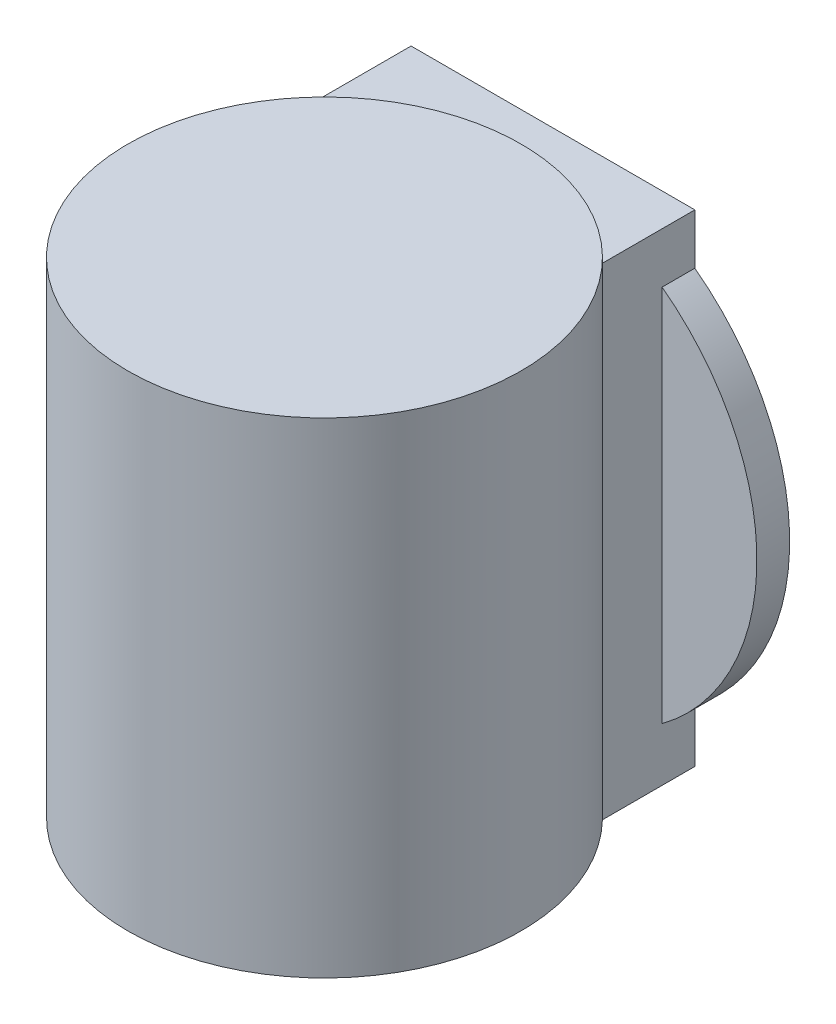
SolidWorks part; units mm, degrees
ref_plane "Front Plane" through (0, 0, 0) normal (0, 0, 1) x (1, 0, 0)
ref_plane "Top Plane" through (0, 0, 0) normal (0, 1, 0) x (1, 0, 0)
ref_plane "Right Plane" through (0, 0, 0) normal (1, 0, 0) x (0, 0, -1)
sketch "Sketch1" plane through (0, 0, 0) normal (0, 1, 0) x (1, 0, 0)
  circle A0 centre (0, 0) radius 0.03
extrude "Boss-Extrude1" add sketch "Sketch1" along normal blind 0.037 and the other way blind 0.037
sketch "Sketch2" plane through (0, 0, 0) normal (0, 0, 1) x (1, 0, 0)
  line L0 (-0.03, -0.037) -> (0.03, -0.037) construction
  line L1 (0.0215, 0.0365) -> (-0.0218, 0.0365)
  line L2 (0.0215, 0.0365) -> (0.0215, -0.037)
  line L3 (0.0215, -0.037) -> (-0.0218, -0.037)
  line L4 (-0.0218, 0.0365) -> (-0.0218, -0.037)
  circle A0 centre (0, 0) radius 0.036
extrude "Boss-Extrude2" add sketch "Sketch2" against normal blind 0.035 contours L2 L3 L4 L1
extrude "Boss-Extrude3" add sketch "Sketch2<3>" against normal blind 0.005 from offset 0.03 contours A0 offset against normal yes
sketch "Sketch2<3>" plane through (0, 0, 0) normal (0, 0, 1) x (1, 0, 0) same geometry as "Sketch2"
sketch "Sketch3" plane through (0, 0, 0) normal (0, 0, 1) x (1, 0, 0)
  circle A0 centre (0, 0) radius 0.0149
  circle A1 centre (0, 0) radius 0.0052
extrude "Boss-Extrude4" add sketch "Sketch3" against normal blind 0.0385
extrude "Boss-Extrude5" add sketch "Sketch3<2>" against normal blind 0.043 contours A1
sketch "Sketch3<2>" plane through (0, 0, 0) normal (0, 0, 1) x (1, 0, 0) same geometry as "Sketch3"
